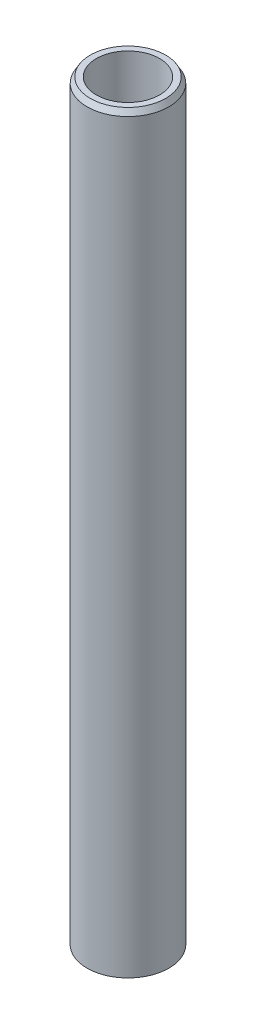
SolidWorks part; units mm, degrees
ref_plane "Front Plane" through (0, 0, 0) normal (0, 0, 1) x (1, 0, 0)
ref_plane "Top Plane" through (0, 0, 0) normal (0, 1, 0) x (1, 0, 0)
ref_plane "Right Plane" through (0, 0, 0) normal (1, 0, 0) x (0, 0, -1)
sketch "Sketch1" plane through (0, 0, 0) normal (0, 1, 0) x (1, 0, 0)
  circle A0 centre (0, 0) radius 32.5
  dimension "SHAFT_OD" = 65
extrude "Boss-Extrude1" add sketch "Sketch1" along normal blind 600
sketch "Sketch2" plane through (0, 0, 0) normal (0, 1, 0) x (1, 0, 0)
  circle A0 centre (0, 0) radius 25.1339
  dimension "BORE_D" = 50.2677
extrude "Cut-Extrude1" cut sketch "Sketch2" along normal through all
chamfer "Chamfer1" distance 4.4677 angle 30 2 edges at (0, 600, 32.5) (0, 0, 32.5) first distance on face at (0, 600, 32.5) first distance on face at (0, 0, 25.1339)
